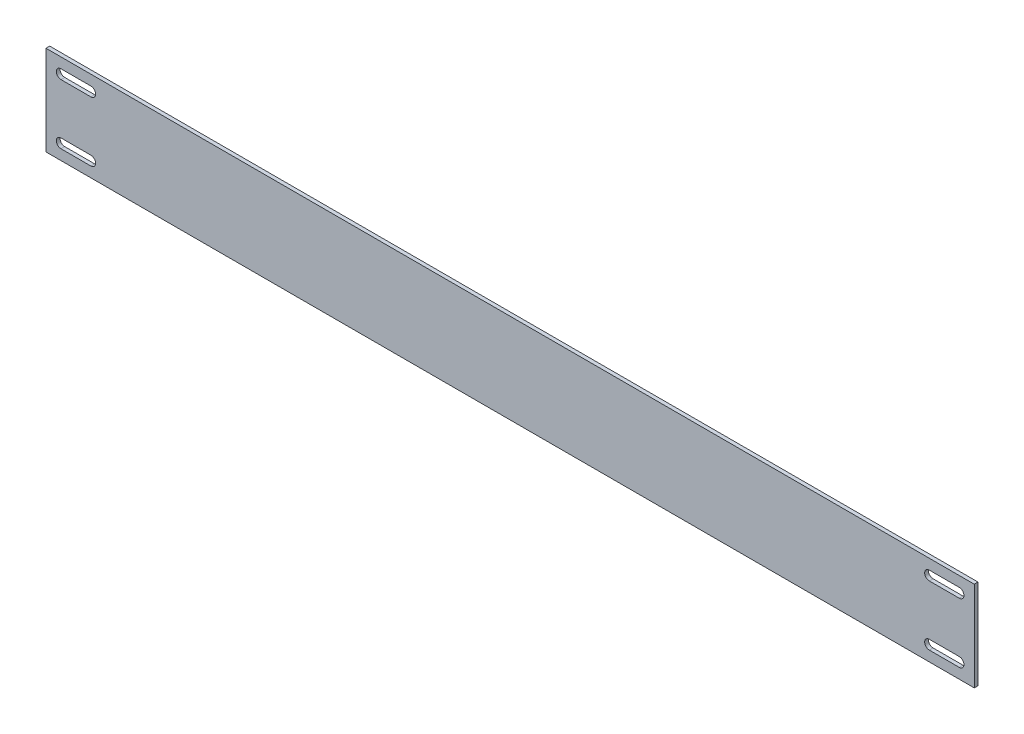
SolidWorks part; units mm, degrees
material "ABS"
ref_plane "Front Plane" through (0, 0, 0) normal (0, 0, 1) x (1, 0, 0)
ref_plane "Top Plane" through (0, 0, 0) normal (0, 1, 0) x (1, 0, 0)
ref_plane "Right Plane" through (0, 0, 0) normal (1, 0, 0) x (0, 0, -1)
sketch "Sketch1" plane through (0, 0, 0) normal (0, 1, 0) x (1, 0, 0)
  line L0 (0, 0) -> (393.7, 0)
  line L1 (393.7, 0) -> (393.7, 1.5875)
  line L2 (393.7, 1.5875) -> (368.3, 1.5875)
  line L5 (0, 0) -> (0, 1.5875)
  line L6 (0, 1.5875) -> (25.4, 1.5875)
  line L8 (25.4, 1.5875) -> (368.3, 1.5875)
  dimension "D1" = 393.7
  dimension "D2" = 25.4
  dimension "D3" = 1.5875
  dimension "D5" = 1.5875
  dimension "D6" = 25.4
extrude "Boss-Extrude1" add sketch "Sketch1" along normal blind 38.1
sketch "Sketch2" plane through (0, 0, -1.5875) normal (0, 0, -1) x (-1, 0, 0)
  line L0 (-196.85, 38.1) -> (-196.85, 0) construction
  line L3 (-25.4, 19.05) -> (0, 19.05) construction
  line L5 (0, 38.1) -> (0, 0) construction
  line L6 (-19.05, 31.75) -> (-6.35, 31.75) construction
  line L7 (-19.05, 33.7344) -> (-6.35, 33.7344)
  line L8 (-19.05, 29.7656) -> (-6.35, 29.7656)
  line L9 (-12.7, 19.05) -> (-12.7, 31.75) construction
  line L10 (-19.05, 6.35) -> (-6.35, 6.35) construction
  line L11 (-19.05, 4.3656) -> (-6.35, 4.3656)
  line L12 (-19.05, 8.3344) -> (-6.35, 8.3344)
  line L13 (-374.65, 6.35) -> (-387.35, 6.35) construction
  line L14 (-374.65, 4.3656) -> (-387.35, 4.3656)
  line L15 (-374.65, 8.3344) -> (-387.35, 8.3344)
  line L16 (-374.65, 31.75) -> (-387.35, 31.75) construction
  line L17 (-374.65, 33.7344) -> (-387.35, 33.7344)
  line L18 (-374.65, 29.7656) -> (-387.35, 29.7656)
  line L19 (0, 38.1) -> (0, 0) construction
  line L20 (-393.7, 38.1) -> (0, 38.1) construction
  line L21 (-393.7, 0) -> (0, 0) construction
  arc A0 (-19.05, 33.7344) -> (-19.05, 29.7656) centre (-19.05, 31.75) ccw
  arc A1 (-6.35, 29.7656) -> (-6.35, 33.7344) centre (-6.35, 31.75) ccw
  arc A2 (-19.05, 4.3656) -> (-19.05, 8.3344) centre (-19.05, 6.35) cw
  arc A3 (-6.35, 8.3344) -> (-6.35, 4.3656) centre (-6.35, 6.35) cw
  arc A4 (-374.65, 4.3656) -> (-374.65, 8.3344) centre (-374.65, 6.35) ccw
  arc A5 (-387.35, 8.3344) -> (-387.35, 4.3656) centre (-387.35, 6.35) ccw
  arc A6 (-374.65, 33.7344) -> (-374.65, 29.7656) centre (-374.65, 31.75) cw
  arc A7 (-387.35, 29.7656) -> (-387.35, 33.7344) centre (-387.35, 31.75) cw
  point P2 (-196.85, 38.1)
  point P14 (-12.7, 31.75)
  point P23 (-12.7, 6.35)
  point P30 (-381, 6.35)
  point P37 (-381, 31.75)
  dimension "D1" = 12.7
  dimension "D2" = 3.9688
  dimension "D3" = 12.7
  dimension "D4" = 12.7
extrude "Cut-Extrude2" cut sketch "Sketch2" against normal through all contours L8 A1 L7 A0 | A3 L12 A2 L11 | L15 A5 L14 A4 | A7 L18 A6 L17 | L18 A7 L17 A6 region at (12.7, 31.75, -1.5875) region at (12.7, 6.35, -1.5875) region at (381, 6.35, -1.5875) region at (381, 31.75, -1.5875)
